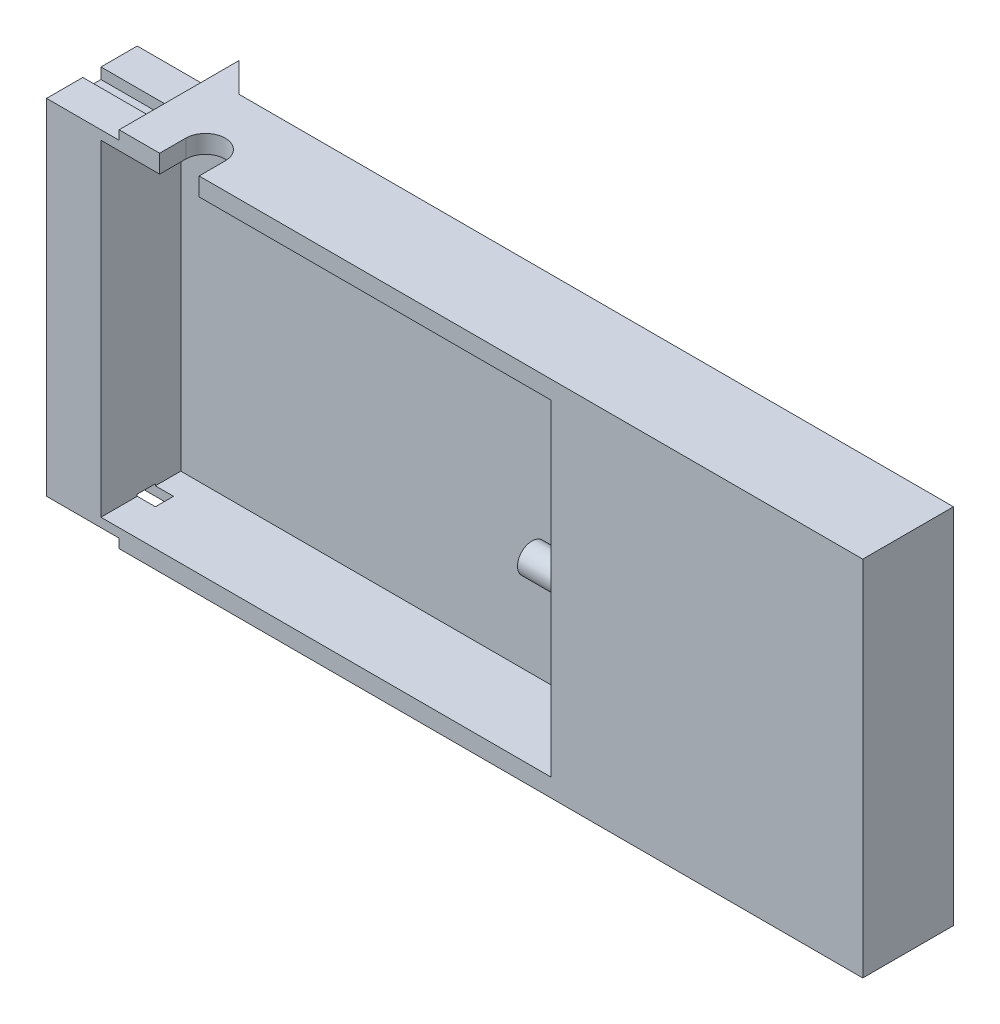
SolidWorks part; units mm, degrees
ref_plane "Front Plane" through (0, 0, 0) normal (0, 0, 1) x (1, 0, 0)
ref_plane "Top Plane" through (0, 0, 0) normal (0, 1, 0) x (1, 0, 0)
ref_plane "Right Plane" through (0, 0, 0) normal (1, 0, 0) x (0, 0, -1)
sketch "Sketch1" plane through (0, 0, 0) normal (0, 0, 1) x (1, 0, 0)
  line L1 (-101.108, 52.0776) -> (68.892, 52.0776)
  line L2 (-101.108, 52.0776) -> (-101.108, -47.9224)
  line L3 (-101.108, -47.9224) -> (68.892, -47.9224)
  line L4 (68.892, 52.0776) -> (68.892, -47.9224)
  dimension "D1" = 100
  dimension "D2" = 170
extrude "Boss-Extrude1" add sketch "Sketch1" along normal blind 15
sketch "Sketch3" plane through (0, 0, 15) normal (0, 0, 1) x (1, 0, 0)
  line L0 (68.892, -47.9224) -> (68.892, 52.0776) construction
  line L9 (-91.108, 47.0776) -> (58.892, 47.0776)
  line L10 (-91.108, 47.0776) -> (-91.108, -42.9224)
  line L11 (-91.108, -42.9224) -> (58.892, -42.9224)
  line L12 (58.892, 47.0776) -> (58.892, -42.9224)
  line L13 (-101.108, 52.0776) -> (-101.108, -47.9224) construction
  line L14 (68.892, 52.0776) -> (-101.108, 52.0776) construction
  line L15 (-101.108, -47.9224) -> (68.892, -47.9224) construction
  line L17 (-91.108, 47.0776) -> (-21.108, 47.0776)
  line L18 (-91.108, 47.0776) -> (-91.108, -42.9224)
  line L19 (-91.108, -42.9224) -> (-21.108, -42.9224)
  line L20 (-21.108, 47.0776) -> (-21.108, -42.9224)
  dimension "D1" = 150
  dimension "D2" = 10
  dimension "D3" = 10
  dimension "D4" = 90
  dimension "D5" = 5
  dimension "D6" = 5
  dimension "D7" = 80
extrude "Cut-Extrude2" cut sketch "Sketch3" against normal blind 12 contours L20 L9 L10 L11 region at (-56.108, 2.0776, 15)
sketch "Sketch8" plane through (0, 52.0776, 0) normal (0, 1, 0) x (1, 0, 0)
  line L0 (68.892, -15) -> (-101.108, -15) construction
  line L1 (-101.108, 0) -> (-86.108, 0)
  line L2 (-101.108, 0) -> (-101.108, -15)
  line L3 (-101.108, -15) -> (-86.108, -15)
  line L4 (-86.108, 0) -> (-86.108, -15)
  dimension "D1" = 15
extrude "Cut-Extrude9" cut sketch "Sketch8" against normal blind 2.5
sketch "Sketch9" plane through (0, -47.9224, 0) normal (0, -1, 0) x (1, 0, 0)
  line L0 (-101.108, 0) -> (68.892, 0) construction
  line L1 (-101.108, 15) -> (-86.108, 15)
  line L2 (-101.108, 15) -> (-101.108, 0)
  line L3 (-101.108, 0) -> (-86.108, 0)
  line L4 (-86.108, 15) -> (-86.108, 0)
  dimension "D1" = 15
extrude "Cut-Extrude10" cut sketch "Sketch9" against normal blind 2.5
sketch "Sketch10" plane through (-21.108, 0, 0) normal (-1, 0, 0) x (0, 0, 1)
  line L4 (15, -42.9224) -> (15, 47.0776)
  line L5 (15, -42.9224) -> (15, 47.0776)
  line L6 (15, 47.0776) -> (3, 47.0776)
  line L7 (15, 47.0776) -> (3, 47.0776)
  line L8 (3, 47.0776) -> (3, -42.9224)
  line L9 (3, 47.0776) -> (3, -42.9224)
  line L10 (3, -42.9224) -> (15, -42.9224)
  line L11 (3, -42.9224) -> (15, -42.9224)
  dimension "D1" = 0
extrude "Cut-Extrude11" cut sketch "Sketch10" against normal blind 58
sketch "Sketch11" plane through (0, 0, 15) normal (0, 0, 1) x (1, 0, 0)
  line L0 (-91.108, -42.9224) -> (36.892, -42.9224) construction
  line L1 (36.892, -42.9224) -> (36.892, 47.0776) construction
  line L2 (-91.108, 47.0776) -> (36.892, 47.0776) construction
  line L3 (-91.108, 47.0776) -> (-91.108, -42.9224) construction
  line L4 (-91.108, -42.9224) -> (36.892, -42.9224)
  line L5 (36.892, -42.9224) -> (36.892, 47.0776)
  line L6 (-91.108, 47.0776) -> (36.892, 47.0776)
  line L7 (-91.108, 47.0776) -> (-91.108, -42.9224)
  line L8 (-86.108, -45.4224) -> (-86.108, -47.9224)
  line L9 (-86.108, -47.9224) -> (68.892, -47.9224)
  line L10 (68.892, -47.9224) -> (68.892, 52.0776)
  line L11 (68.892, 52.0776) -> (-86.108, 52.0776)
  line L12 (-86.108, 52.0776) -> (-86.108, 49.5776)
  line L13 (-86.108, 49.5776) -> (-101.108, 49.5776)
  line L14 (-101.108, 49.5776) -> (-101.108, -45.4224)
  line L15 (-101.108, -45.4224) -> (-86.108, -45.4224)
  line L16 (-86.108, -45.4224) -> (-86.108, -47.9224)
  line L17 (-86.108, -47.9224) -> (68.892, -47.9224)
  line L18 (68.892, -47.9224) -> (68.892, 52.0776)
  line L19 (68.892, 52.0776) -> (-86.108, 52.0776)
  line L20 (-86.108, 52.0776) -> (-86.108, 49.5776)
  line L21 (-86.108, 49.5776) -> (-101.108, 49.5776)
  line L22 (-101.108, 49.5776) -> (-101.108, -45.4224)
  line L23 (-101.108, -45.4224) -> (-86.108, -45.4224)
  dimension "D1" = 0
extrude "Boss-Extrude2" add sketch "Sketch11" along normal blind 10
sketch "Sketch12" plane through (36.892, 0, 0) normal (-1, 0, 0) x (0, 0, 1)
  line L5 (3, 47.0776) -> (25, 47.0776)
  line L6 (3, 47.0776) -> (3, -42.9224)
  line L7 (3, -42.9224) -> (25, -42.9224)
  line L8 (25, 47.0776) -> (25, -42.9224)
extrude "Boss-Extrude4" add sketch "Sketch12" along normal blind 4
sketch "Sketch14" plane through (0, 52.0776, 0) normal (0, 1, 0) x (1, 0, 0)
  line L0 (-86.108, 0) -> (-78.108, 0)
  line L1 (68.892, 0) -> (-86.108, 0) construction
  line L2 (-78.108, 0) -> (-86.108, 8)
  line L3 (-86.108, -21) -> (-86.108, 55) construction
  line L4 (-86.108, 8) -> (-86.108, 0)
  dimension "D1" = 8
  dimension "D2" = 8
extrude "Boss-Extrude6" add sketch "Sketch14" against normal blind 100
sketch "Sketch15" plane through (-101.108, 0, 0) normal (-1, 0, 0) x (0, 0, 1)
  line L5 (12.5, -45.4224) -> (12.5, 49.5776) construction
  line L6 (0, -45.4224) -> (25, -45.4224)
  line L8 (0, -45.4224) -> (0, 49.5776)
  line L9 (0, 49.5776) -> (25, 49.5776)
  line L10 (25, -45.4224) -> (25, 49.5776)
  line L17 (10, -45.4224) -> (10, -42.4224)
  line L18 (10, -42.4224) -> (15, -42.4224)
  line L19 (15, -45.4224) -> (15, -42.4224)
  line L20 (12.5, -45.4224) -> (15, -42.4224) construction
  line L21 (10, -42.4224) -> (12.5, -45.4224) construction
  line L22 (10, 46.5776) -> (15, 46.5776)
  line L23 (10, 46.5776) -> (10, 49.5776)
  line L25 (15, 46.5776) -> (15, 49.5776)
  line L26 (10, 46.5776) -> (12.5, 49.5776) construction
  line L27 (12.5, 49.5776) -> (15, 46.5776) construction
  point P12 (10, 48.0776)
  dimension "D1" = 5
  dimension "D2" = 3
  dimension "D3" = 5
  dimension "D4" = 2.5
  dimension "D5" = 2.5
  dimension "D6" = 3
extrude "Cut-Extrude14" cut sketch "Sketch15" against normal blind 15 contours L22 L25 L9 L23 | L6 L19 L18 L17 region at (-101.108, -43.9224, 12.5) region at (-101.108, 48.0776, 12.5)
sketch "Sketch16" plane through (68.892, 0, 0) normal (1, 0, 0) x (0, 0, -1)
  line L4 (0, -47.9224) -> (0, 52.0776)
  line L5 (0, 52.0776) -> (-25, 52.0776)
  line L6 (-25, 52.0776) -> (-25, -47.9224)
  line L7 (-25, -47.9224) -> (0, -47.9224)
  line L8 (0, -47.9224) -> (0, 52.0776)
  line L9 (0, 52.0776) -> (-25, 52.0776)
  line L10 (-25, 52.0776) -> (-25, -47.9224)
  line L11 (-25, -47.9224) -> (0, -47.9224)
  dimension "D1" = 0
extrude "Boss-Extrude7" add sketch "Sketch16" along normal blind 50
sketch "Sketch17" plane through (0, 0, 0) normal (0, 0, -1) x (-1, 0, 0)
  line L0 (78.108, -47.9224) -> (-118.892, -47.9224) construction
  line L1 (-43.892, -32.9224) -> (-113.892, -32.9224)
  line L2 (-43.892, -32.9224) -> (-43.892, 37.0776)
  line L3 (-43.892, 37.0776) -> (-113.892, 37.0776)
  line L4 (-113.892, -32.9224) -> (-113.892, 37.0776)
  line L5 (-118.892, -47.9224) -> (-118.892, 52.0776) construction
  dimension "D1" = 70
  dimension "D2" = 70
  dimension "D3" = 15
  dimension "D4" = 5
extrude "Cut-Extrude15" cut sketch "Sketch17" against normal blind 22
sketch "Sketch18" plane through (0, 0, 0) normal (0, 0, -1) x (-1, 0, 0)
  line L1 (-113.892, -32.9224) -> (-43.892, -32.9224)
  line L2 (-113.892, -32.9224) -> (-113.892, 37.0776)
  line L3 (-113.892, 37.0776) -> (-43.892, 37.0776)
  line L4 (-43.892, -32.9224) -> (-43.892, 37.0776)
  line L5 (-115.892, -34.9224) -> (-41.892, -34.9224)
  line L6 (-115.892, -34.9224) -> (-115.892, 39.0776)
  line L7 (-115.892, 39.0776) -> (-41.892, 39.0776)
  line L8 (-41.892, -34.9224) -> (-41.892, 39.0776)
  dimension "D1" = 2
  dimension "D2" = 2
  dimension "D3" = 2
  dimension "D4" = 2
extrude "Cut-Extrude16" cut sketch "Sketch18" against normal blind 4
sketch "Sketch19" plane through (-101.108, 0, 0) normal (-1, 0, 0) x (0, 0, 1)
  line L12 (10, 46.5776) -> (10, 49.5776)
  line L13 (10, 49.5776) -> (0, 49.5776)
  line L14 (0, 49.5776) -> (0, -45.4224)
  line L15 (0, -45.4224) -> (10, -45.4224)
  line L16 (10, -45.4224) -> (10, -42.4224)
  line L17 (10, -42.4224) -> (15, -42.4224)
  line L18 (15, -42.4224) -> (15, -45.4224)
  line L19 (15, -45.4224) -> (25, -45.4224)
  line L20 (25, -45.4224) -> (25, 49.5776)
  line L21 (25, 49.5776) -> (15, 49.5776)
  line L22 (15, 49.5776) -> (15, 46.5776)
  line L23 (15, 46.5776) -> (10, 46.5776)
  line L24 (10, 46.5776) -> (10, 49.5776)
  line L25 (10, 49.5776) -> (0, 49.5776)
  line L26 (0, 49.5776) -> (0, -45.4224)
  line L27 (0, -45.4224) -> (10, -45.4224)
  line L28 (10, -45.4224) -> (10, -42.4224)
  line L29 (10, -42.4224) -> (15, -42.4224)
  line L30 (15, -42.4224) -> (15, -45.4224)
  line L31 (15, -45.4224) -> (25, -45.4224)
  line L32 (25, -45.4224) -> (25, 49.5776)
  line L33 (25, 49.5776) -> (15, 49.5776)
  line L34 (15, 49.5776) -> (15, 46.5776)
  line L35 (15, 46.5776) -> (10, 46.5776)
  dimension "D1" = 0
extrude "Boss-Extrude8" add sketch "Sketch19" along normal blind 5
sketch "Sketch20" plane through (43.892, 0, 0) normal (1, 0, 0) x (0, 0, -1)
  circle A0 centre (-18.1819, 0) radius 3
  circle A1 centre (-18.1819, 0) radius 4
extrude "Boss-Extrude9" add sketch "Sketch20" against normal blind 23
extrude "Cut-Extrude17" cut sketch "Sketch20<2>" against normal blind 23 contours A0
sketch "Sketch20<2>" plane through (43.892, 0, 0) normal (1, 0, 0) x (0, 0, -1) same geometry as "Sketch20"
sketch "Sketch21" plane through (0, 52.0776, 0) normal (0, 1, 0) x (1, 0, 0)
  line L0 (-69.4942, -25) -> (-69.4942, -17.7977) construction
  line L4 (118.892, -25) -> (-86.108, -25) construction
  line L5 (-74.9292, -25) -> (-74.9292, -17.7977)
  line L6 (-64.0591, -25) -> (-64.0591, -17.7977)
  arc A2 (-74.9292, -25) -> (-64.0591, -25) centre (-69.4942, -25) ccw
  arc A3 (-64.0591, -17.7977) -> (-74.9292, -17.7977) centre (-69.4942, -17.7977) ccw
  point P4 (-69.4942, -21.3989)
extrude "Cut-Extrude18" cut sketch "Sketch21" against normal blind 23 contours L6 A3 L5 A2
